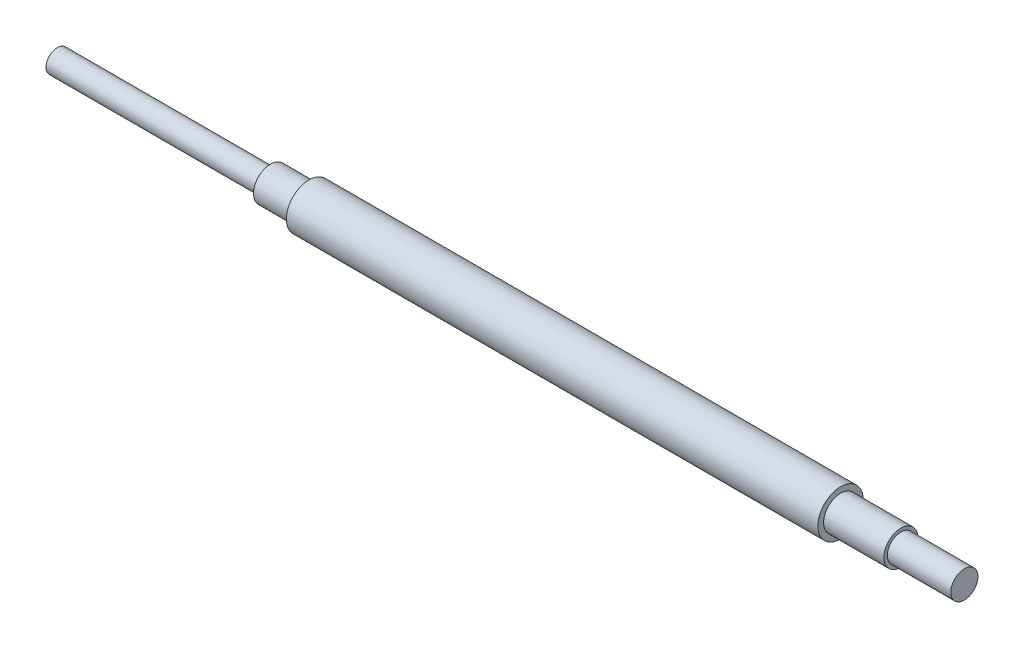
SolidWorks part; units mm, degrees
ref_plane "Front Plane" through (0, 0, 0) normal (0, 0, 1) x (1, 0, 0)
ref_plane "Top Plane" through (0, 0, 0) normal (0, 1, 0) x (1, 0, 0)
ref_plane "Right Plane" through (0, 0, 0) normal (1, 0, 0) x (0, 0, -1)
sketch "Sketch1" plane through (0, 0, 0) normal (0, 0, 1) x (1, 0, 0)
  line L3 (-7.8966, 3.81) -> (-7.8966, 0)
  line L4 (-7.8966, 3.81) -> (-25.6766, 3.81)
  line L5 (-25.6766, 3.81) -> (-25.6766, 4.7625)
  line L6 (-25.6766, 4.7625) -> (-42.5676, 4.7625)
  line L7 (-42.5676, 4.7625) -> (-42.5676, 6.35)
  line L8 (-42.5676, 6.35) -> (-191.4116, 6.35)
  line L9 (-191.4116, 6.35) -> (-191.4116, 4.7625)
  line L10 (-191.4116, 4.7625) -> (-202.2066, 4.7625)
  line L11 (-202.2066, 4.7625) -> (-202.2066, 3.175)
  line L12 (-202.2066, 3.175) -> (-261.8966, 3.175)
  line L13 (-261.8966, 3.175) -> (-261.8966, 0)
  line L14 (-261.8966, 0) -> (-7.8966, 0)
  line L16 (-191.4116, -5.0403) -> (-191.4116, 5.0403) construction
  line L18 (0, 0) -> (27.519, 0) construction
  line L19 (-253.0066, 10.16) -> (-253.0066, -10.16) construction
  point P1 (-16.7572, 0)
  point P2 (-7.1653, 0)
  point P17 (-6.6266, 0)
  point P20 (-24.4066, 4.7625)
  dimension "D1" = 6.35
  dimension "D2" = 254
  dimension "D3" = 4.7625
  dimension "D4" = 3.175
  dimension "D5" = 17.78
  dimension "D6" = 3.81
  dimension "D7" = 148.844
  dimension "D8" = 10.795
  dimension "D9" = 8.89
revolve "Revolve1" add sketch "Sketch1" angle 360 about L14
equation "\"CompressorInnerDiameter\"=0.125"
equation "\"D4@Sketch1\"=\"CompressorInnerDiameter\""
